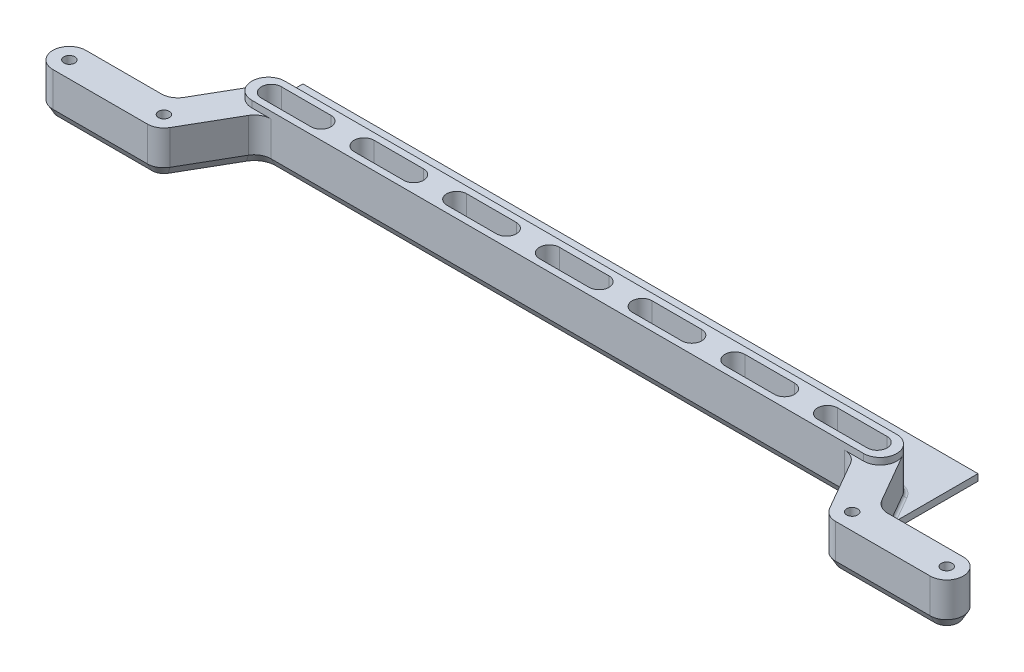
SolidWorks part; units mm, degrees
ref_plane "前视基准面" through (0, 0, 0) normal (0, 0, 1) x (1, 0, 0)
ref_plane "上视基准面" through (0, 0, 0) normal (0, 1, 0) x (1, 0, 0)
ref_plane "右视基准面" through (0, 0, 0) normal (1, 0, 0) x (0, 0, -1)
sketch "草图1" plane through (0, 0, 0) normal (0, 1, 0) x (1, 0, 0)
  line L0 (-14.275, 0) -> (14.275, 0) construction
  line L1 (-14.275, 5) -> (14.275, 5)
  line L2 (-14.275, -5) -> (14.275, -5)
  line L3 (14.275, 0) -> (25.822, -20) construction
  line L4 (25.822, -20) -> (210.628, -20) construction
  line L5 (14.275, 0) -> (25.822, -20) construction
  line L6 (18.6051, 2.5) -> (30.1521, -17.5)
  line L7 (9.9449, -2.5) -> (21.4919, -22.5)
  line L8 (25.822, -20) -> (210.628, -20) construction
  line L9 (25.822, -15) -> (210.628, -15)
  line L10 (25.822, -25) -> (210.628, -25)
  line L11 (210.628, -20) -> (222.175, 0) construction
  line L12 (206.2979, -17.5) -> (217.8449, 2.5)
  line L13 (214.9581, -22.5) -> (226.5051, -2.5)
  line L14 (222.175, 0) -> (250.725, 0) construction
  line L15 (222.175, 5) -> (250.725, 5)
  line L16 (222.175, -5) -> (250.725, -5)
  circle A0 centre (-14.275, 0) radius 1.65
  arc A1 (-14.275, 5) -> (-14.275, -5) centre (-14.275, 0) ccw
  arc A2 (14.275, -5) -> (14.275, 5) centre (14.275, 0) ccw
  arc A3 (18.6051, 2.5) -> (9.9449, -2.5) centre (14.275, 0) ccw
  arc A4 (21.4919, -22.5) -> (30.1521, -17.5) centre (25.822, -20) ccw
  arc A5 (25.822, -15) -> (25.822, -25) centre (25.822, -20) ccw
  arc A6 (210.628, -25) -> (210.628, -15) centre (210.628, -20) ccw
  circle A7 centre (14.275, 0) radius 1.65
  arc A8 (206.2979, -17.5) -> (214.9581, -22.5) centre (210.628, -20) ccw
  arc A9 (226.5051, -2.5) -> (217.8449, 2.5) centre (222.175, 0) ccw
  arc A10 (222.175, 5) -> (222.175, -5) centre (222.175, 0) ccw
  arc A11 (250.725, -5) -> (250.725, 5) centre (250.725, 0) ccw
  circle A12 centre (250.725, 0) radius 1.65
  circle A13 centre (222.175, 0) radius 1.65
  point P2 (0, 0)
  point P12 (20.0485, -10)
  point P18 (118.225, -20)
  point P27 (216.4015, -10)
  point P34 (236.45, 0)
  dimension "D1" = 3.3
  dimension "D2" = 5
  dimension "D7" = 3.3
  dimension "D11" = 3.3
  dimension "D12" = 3.3
  dimension "D3" = 28.55
  dimension "D4" = 20
  dimension "D5" = 120
  dimension "D6" = 120
  dimension "D8" = 20
  dimension "D9" = 28.55
  dimension "D10" = 207.9
extrude "凸台-拉伸1" add sketch "草图1" along normal blind 15 contours A3 L1 A1 L2 L7 A0 | A2 A3 L7 L2 | A5 L9 L6 A2 L2 L7 | L9 A5 A4 L6 | L10 A6 L9 L6 A4 | A10 L12 L9 A6 L13 L16 | L12 A8 A6 L9 | A9 A10 L16 L13 A13 | L16 A11 L15 A9 L13 A12 region at (-3.682, 0, -0.0218) region at (16.7043, 0, -4.2077) region at (20.0485, 0, 10) region at (118.225, 0, 20.0068) region at (25.8655, 0, 19.9247) region at (216.4015, 0, 10) region at (210.5845, 0, 19.9247) region at (219.7457, 0, -4.2077) region at (240.132, 0, -0.0218)
fillet "圆角1" radius 5 4 edges at (11.3882, 7.5, 5) (225.0618, 7.5, 5) (207.7412, 7.5, 15) (28.7088, 7.5, 15)
chamfer "倒角1" distance 1.5 angle 60 20 edges at (213.5147, 0, 5) (219.675, 0, -4.3301) (236.45, 0, -5) (255.725, 0, 0) (239.3368, 0, 5) (225.4485, 0, 5.6699) (219.2882, 0, 15) (213.128, 0, 24.3301) (118.225, 0, 25) (23.322, 0, 24.3301) (22.9353, 0, 5) (17.1618, 0, 15) (16.775, 0, -4.3301) (11.0015, 0, 5.6699) (0, 0, -5) (-2.8868, 0, 5) (-19.275, 0, 0) (207.3545, 0, 14.3301) (118.225, 0, 15) (29.0955, 0, 14.3301) first distance on face at (118.225, 0, 8)
sketch "草图3" plane through (0, 0, 0) normal (0, 1, 0) x (1, 0, 0)
  circle A0 centre (-14.275, 0) radius 2.5
  circle A1 centre (14.275, 0) radius 2.5
  circle A2 centre (14.275, 0) radius 1.65 construction
  circle A3 centre (-14.275, 0) radius 1.65 construction
  circle A4 centre (250.725, 0) radius 2.5
  circle A5 centre (222.175, 0) radius 2.5
  circle A6 centre (222.175, 0) radius 1.65 construction
  circle A7 centre (250.725, 0) radius 1.65 construction
  dimension "D1" = 5
  dimension "D2" = 5
  dimension "D3" = 5
  dimension "D4" = 5
extrude "切除-拉伸1" cut sketch "草图3" along normal blind 3
sketch "草图4" plane through (0, 15, 0) normal (0, 1, 0) x (1, 0, 0)
  line L0 (25.822, -25) -> (210.628, -25) construction
  line L1 (-49.5799, -15) -> (304.1802, -15)
  line L2 (-49.5799, -15) -> (-49.5799, 56.9164)
  line L3 (-49.5799, 56.9164) -> (304.1802, 56.9164)
  line L4 (304.1802, -15) -> (304.1802, 56.9164)
  dimension "D1" = 10
extrude "切除-拉伸2" cut sketch "草图4" against normal blind 2
fillet "圆角2" radius 5 2 edges at (17.1618, 14, 15) (219.2882, 14, 15)
sketch "草图5" plane through (0, 15, 0) normal (0, 1, 0) x (1, 0, 0)
  line L0 (110.725, -20) -> (125.725, -20) construction
  line L1 (110.725, -17) -> (125.725, -17)
  line L2 (110.725, -23) -> (125.725, -23)
  line L3 (118.225, -20) -> (118.225, -15) construction
  line L4 (25.822, -15) -> (210.628, -15) construction
  arc A0 (110.725, -17) -> (110.725, -23) centre (110.725, -20) ccw
  arc A1 (125.725, -23) -> (125.725, -17) centre (125.725, -20) ccw
  point P2 (118.225, -20)
  dimension "D2" = 3
  dimension "D1" = 5
  dimension "D3" = 15
extrude "切除-拉伸3" cut sketch "草图5" against normal blind 12
pattern_linear "阵列(线性)1" count 4 spacing 28 along (1, 0, 0) count 4 spacing 28 along (-1, 0, 0) of "切除-拉伸3"
sketch "草图6" plane through (0, 0, 0) normal (0, -1, 0) x (1, 0, 0)
  line L0 (210.628, 23.5) -> (25.822, 23.5) construction
  line L1 (25.5333, 23.5) -> (210.3393, 23.5)
  line L2 (16.275, 23) -> (16.275, 40)
  line L3 (16.275, 40) -> (220.175, 40)
  line L4 (220.175, 23.5) -> (220.175, 40)
  line L5 (25.822, 25) -> (210.628, 25) construction
  line L6 (220.175, 23.5) -> (220.175, 6.4641)
  line L7 (220.175, 6.4641) -> (210.3393, 23.5)
  line L8 (222.3193, 6.75) -> (213.6591, 21.75) construction
  line L9 (16.275, 23) -> (16.275, 7.4641)
  line L10 (16.275, 7.4641) -> (25.5333, 23.5)
  line L11 (22.7909, 21.75) -> (14.1307, 6.75) construction
  circle A0 centre (14.275, 0) radius 1.65 construction
  circle A1 centre (222.175, 0) radius 1.65 construction
  dimension "D1" = 15
  dimension "D2" = 2
  dimension "D3" = 2
  dimension "D4" = 2
  dimension "D5" = 1.5
extrude "凸台-拉伸2" add sketch "草图6" against normal blind 2
ref_plane "基准面1" through (0, 0, 50) normal (0, 0, 1) x (1, 0, 0)
mirror "镜向2" about plane through (0, 0, 50) normal (0, 0, 1) of bodies 111
sketch "草图7" plane through (0, 0, 0) normal (0, -1, 0) x (-1, 0, 0)
  line L1 (55.4017, 17.1219) -> (-285.345, 17.1219)
  line L2 (55.4017, 17.1219) -> (55.4017, -46.9179)
  line L3 (55.4017, -46.9179) -> (-285.345, -46.9179)
  line L4 (-285.345, 17.1219) -> (-285.345, -46.9179)
extrude "切除-拉伸4" cut sketch "草图7" against normal through all
fillet "圆角3" radius 1 5 edges at (217.417, 2, 82.4496) (212.9553, 2, 75.9689) (118.225, 2, 75.3453) (23.4947, 2, 75.9689) (19.033, 2, 82.4496)
